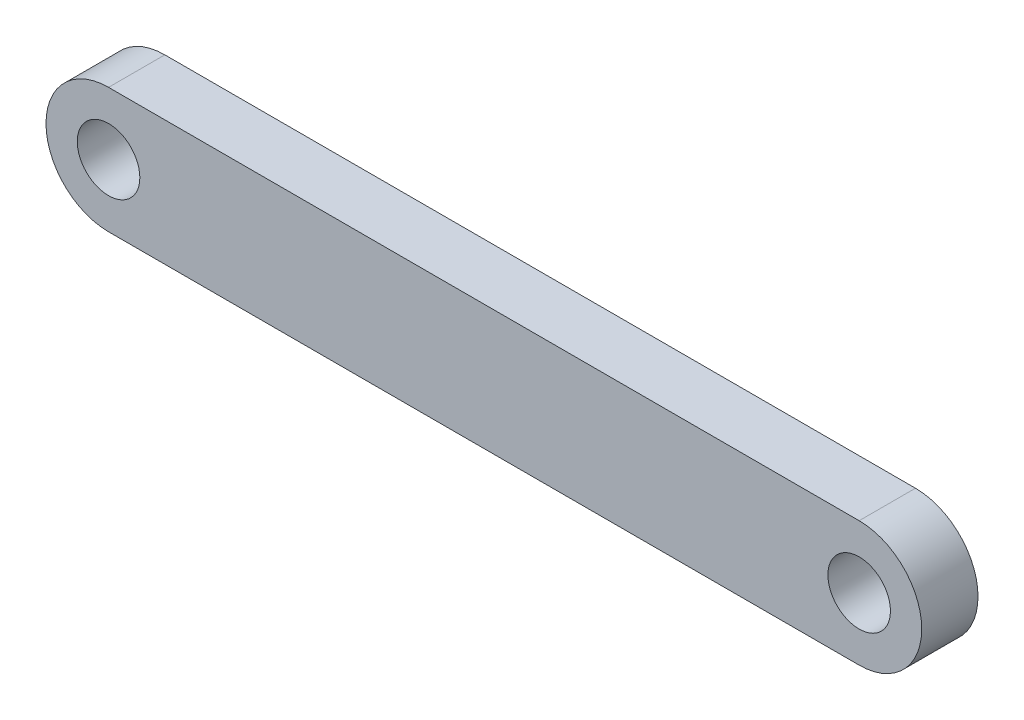
SolidWorks part; units mm, degrees
material "ABS"
ref_plane "Front Plane" through (0, 0, 0) normal (0, 0, 1) x (1, 0, 0)
ref_plane "Top Plane" through (0, 0, 0) normal (0, 1, 0) x (1, 0, 0)
ref_plane "Right Plane" through (0, 0, 0) normal (1, 0, 0) x (0, 0, -1)
ref_axis "X" through (-44, 0, 0) along (1, 0, 0)
ref_axis "Y" through (0, 11, 0) along (0, -1, 0)
ref_axis "Z" through (0, 0, -4.95) along (0, 0, 1)
sketch "Sketch1" plane through (0, 0, 0) normal (0, 0, 1) x (1, 0, 0)
  line L0 (-60, 0) -> (60, 0) construction
  line L1 (-60, 10) -> (60, 10)
  line L2 (-60, -10) -> (60, -10)
  arc A0 (-60, 10) -> (-60, -10) centre (-60, 0) ccw
  arc A1 (60, -10) -> (60, 10) centre (60, 0) ccw
  circle A2 centre (-60, 0) radius 5
  circle A3 centre (60, 0) radius 5
  point P2 (0, 0)
  dimension "D1" = 5
  dimension "D3" = 10
  dimension "D2" = 120
extrude "Boss-Extrude1" add sketch "Sketch1" along normal mid plane 9
